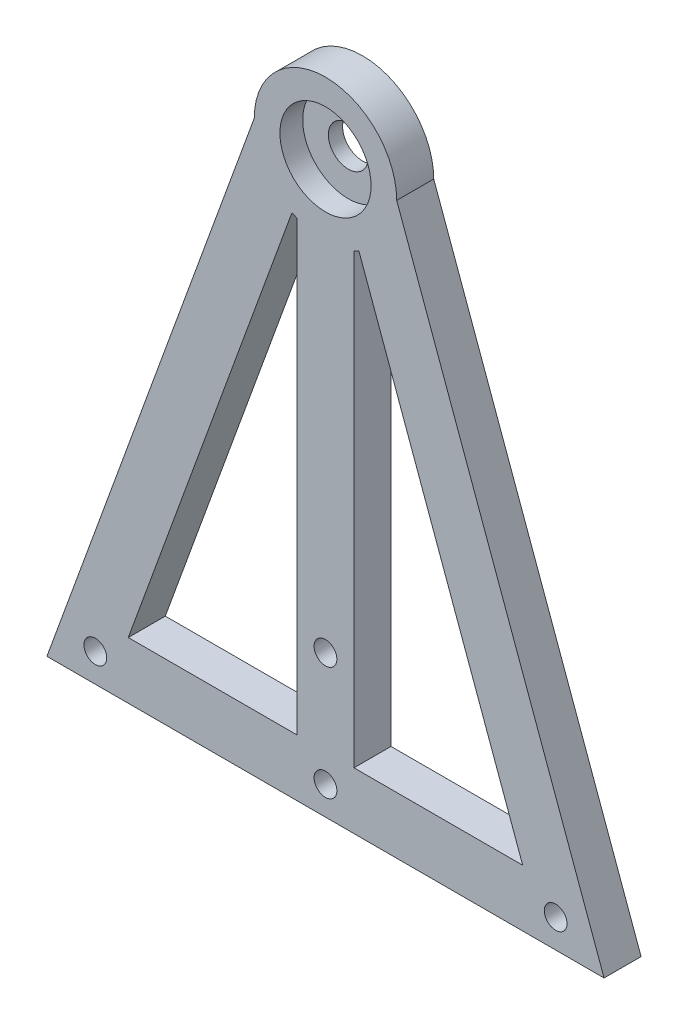
SolidWorks part; units mm, degrees
ref_plane "Front Plane" through (0, 0, 0) normal (0, 0, 1) x (1, 0, 0)
ref_plane "Top Plane" through (0, 0, 0) normal (0, 1, 0) x (1, 0, 0)
ref_plane "Right Plane" through (0, 0, 0) normal (1, 0, 0) x (0, 0, -1)
sketch "Sketch1" plane through (0, 0, 0) normal (0, 0, 1) x (1, 0, 0)
  line L0 (0, 0) -> (0, 100)
  line L1 (-48.897, 0) -> (48.897, 0)
  line L2 (-12.5, 100) -> (-48.897, 0)
  line L3 (12.5, 100) -> (48.897, 0)
  line L4 (0, 0) -> (0, 10)
  line L5 (-5.8742, 88.9662) -> (-34.6155, 10)
  line L6 (-34.6155, 10) -> (34.6155, 10)
  line L7 (5.8742, 88.9662) -> (34.6155, 10)
  line L8 (-3.1031, 96.5798) -> (-34.6155, 10) construction
  line L9 (3.1031, 96.5798) -> (34.6155, 10) construction
  line L10 (-5, 10) -> (5, 10)
  line L11 (-5, 10) -> (-5, 88.5436)
  line L12 (5, 10) -> (5, 88.5436)
  line L14 (-12.5, 100) -> (-48.897, 0) construction
  line L15 (0, 100) -> (0, 50) construction
  circle A2 centre (0, 100) radius 12.5
  arc A3 (12.5, 100) -> (5.8742, 88.9662) centre (0, 100) cw
  arc A4 (-5.8742, 88.9662) -> (-12.5, 100) centre (0, 100) cw
  arc A5 (-5, 88.5436) -> (5, 88.5436) centre (0, 100) ccw
  point P8 (0, 0)
  point P21 (0, 10)
  point P24 (0, 0)
  point P26 (59.2974, -28.5749)
  dimension "D2" = 25
  dimension "D1" = 100
  dimension "D3" = 70
  dimension "D4" = 10
  dimension "D6" = 10
  dimension "D7" = 50
  dimension "D5" = 10
extrude "Boss-Extrude1" add sketch "Sketch1" along normal blind 6.5 contours A2 | A4 L2 L1 L3 A3 L7 L6 L5 | L11 A5 L12 L10
sketch "Sketch2" plane through (0, 0, 6.5) normal (0, 0, 1) x (1, 0, 0)
  arc A0 (12.5, 100) -> (-12.5, 100) centre (0, 100) ccw construction
  arc A1 (12.5, 100) -> (-12.5, 100) centre (0, 100) ccw
  circle A2 centre (0, 100) radius 3.5
  circle A3 centre (0, 100) radius 8
  dimension "D1" = 7
  dimension "D2" = 16
extrude "Cut-Extrude1" cut sketch "Sketch2" against normal up to next contours A2
extrude "Cut-Extrude2" cut sketch "Sketch2<3>" against normal blind 4 contours A3 A2 region at (-7.7737, 100, 6.5)
sketch "Sketch2<3>" plane through (0, 0, 6.5) normal (0, 0, 1) x (1, 0, 0) same geometry as "Sketch2"
sketch "Sketch3" plane through (0, 0, 6.5) normal (0, 0, 1) x (1, 0, 0)
  line L1 (5.8742, 88.9662) -> (34.6155, 10) construction
  line L2 (5, 10) -> (34.6155, 10) construction
  line L3 (5, 10) -> (5, 88.5436) construction
  line L4 (-5, 10) -> (-5, 88.5436) construction
  line L5 (-5.8742, 88.9662) -> (-34.6155, 10) construction
  line L6 (-34.6155, 10) -> (-5, 10) construction
  line L7 (-12.5, 100) -> (-48.897, 0) construction
  line L8 (-48.897, 0) -> (48.897, 0) construction
  line L10 (5.8742, 88.9662) -> (34.6155, 10) construction
  line L11 (5, 10) -> (34.6155, 10) construction
  line L12 (5, 10) -> (5, 88.5436) construction
  line L13 (-5, 10) -> (-5, 88.5436) construction
  line L14 (-5.8742, 88.9662) -> (-34.6155, 10) construction
  line L15 (-34.6155, 10) -> (-5, 10) construction
  line L16 (-12.5, 100) -> (-48.897, 0) construction
  line L17 (-48.897, 0) -> (48.897, 0) construction
  line L18 (-48.897, 0) -> (-48.897, 5) construction
  line L20 (-48.897, 5) -> (48.897, 5) construction
  line L21 (-48.897, 5) -> (-40.397, 5) construction
  line L22 (48.897, 5) -> (40.397, 5) construction
  line L23 (0, 100) -> (0, 5) construction
  line L24 (0, 100) -> (0, 25) construction
  arc A0 (5, 88.5436) -> (5.8742, 88.9662) centre (0, 100) ccw construction
  arc A1 (-5.8742, 88.9662) -> (-5, 88.5436) centre (0, 100) ccw construction
  circle A2 centre (0, 100) radius 8 construction
  arc A3 (12.5, 100) -> (-12.5, 100) centre (0, 100) ccw construction
  arc A4 (5, 88.5436) -> (5.8742, 88.9662) centre (0, 100) ccw construction
  arc A5 (-5.8742, 88.9662) -> (-5, 88.5436) centre (0, 100) ccw construction
  circle A6 centre (0, 100) radius 8 construction
  arc A7 (12.5, 100) -> (-12.5, 100) centre (0, 100) ccw construction
  circle A8 centre (0, 5) radius 2
  circle A9 centre (40.397, 5) radius 2
  circle A10 centre (-40.397, 5) radius 2
  circle A11 centre (0, 25) radius 2
  circle A12 centre (-40.397, 5) radius 4
  circle A13 centre (0, 5) radius 4
  circle A14 centre (40.397, 5) radius 4
  circle A15 centre (0, 25) radius 4
  dimension "D6" = 4
  dimension "D7" = 4
  dimension "D8" = 4
  dimension "D9" = 4
  dimension "D10" = 8
  dimension "D11" = 8
  dimension "D12" = 8
  dimension "D13" = 8
  dimension "D1" = 5
  dimension "D2" = 5
  dimension "D3" = 8.5
  dimension "D4" = 8.5
  dimension "D5" = 75
extrude "Cut-Extrude4" cut sketch "Sketch3" against normal up to next contours A10 | A8 | A9 | A11 region at (0, 5, 6.5) region at (40.397, 5, 6.5) region at (-40.397, 5, 6.5)
